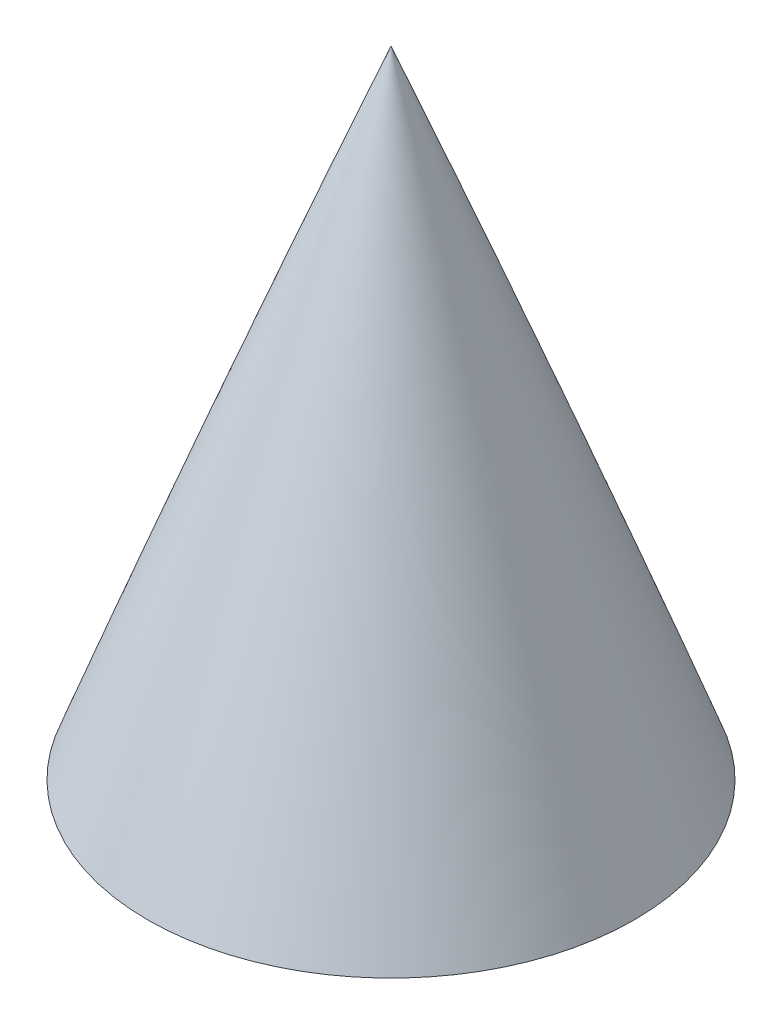
SolidWorks part; units mm, degrees
material "PVB"
ref_plane "Front Plane" through (0, 0, 0) normal (0, 0, 1) x (1, 0, 0)
ref_plane "Top Plane" through (0, 0, 0) normal (0, 1, 0) x (1, 0, 0)
ref_plane "Right Plane" through (0, 0, 0) normal (1, 0, 0) x (0, 0, -1)
sketch "Sketch2" plane through (0, 0, 0) normal (0, 0, 1) x (1, 0, 0)
  line L0 (0, 0) -> (0, 355.6) construction
  line L1 (-76.2, 0) -> (-69.85, 0)
  line L2 (0, 355.6) -> (0, 350.52)
  line L3 (0, 350.52) -> (0, 0)
  line L4 (0, 0) -> (-69.85, 0)
  arc A0 (0, 355.6) -> (-76.2, 0) centre (1016.1023, -48.1005) ccw
  dimension "D1" = 355.6
  dimension "D2" = 5.08
  dimension "D3" = 76.2
  dimension "D4" = 6.35
revolve "Revolve1" add sketch "Sketch2" angle 360 about L2
sketch "Sketch3" plane through (0, 0, 0) normal (0, -1, 0) x (1, 0, 0)
  circle A0 centre (0, 0) radius 88.9
  circle A1 centre (0, 0) radius 86.995
  dimension "D1" = 177.8
extrude "Boss-Extrude1" [suppressed] add sketch "Sketch3" along normal blind 35.56
sketch "Sketch7" plane through (0, 0, 0) normal (0, -1, 0) x (1, 0, 0)
  circle A0 centre (-188.315, 83.0177) radius 421.4958
extrude "Cut-Extrude2" cut sketch "Sketch7" against normal blind 330.2
sketch "Sketch8" plane through (0, 330.2, 0) normal (0, -1, 0) x (-1, 0, 0)
  circle A0 centre (0, 0) radius 2.413
  dimension "D1" = 4.826
extrude "Cut-Extrude3" cut sketch "Sketch8" against normal blind 12.7
